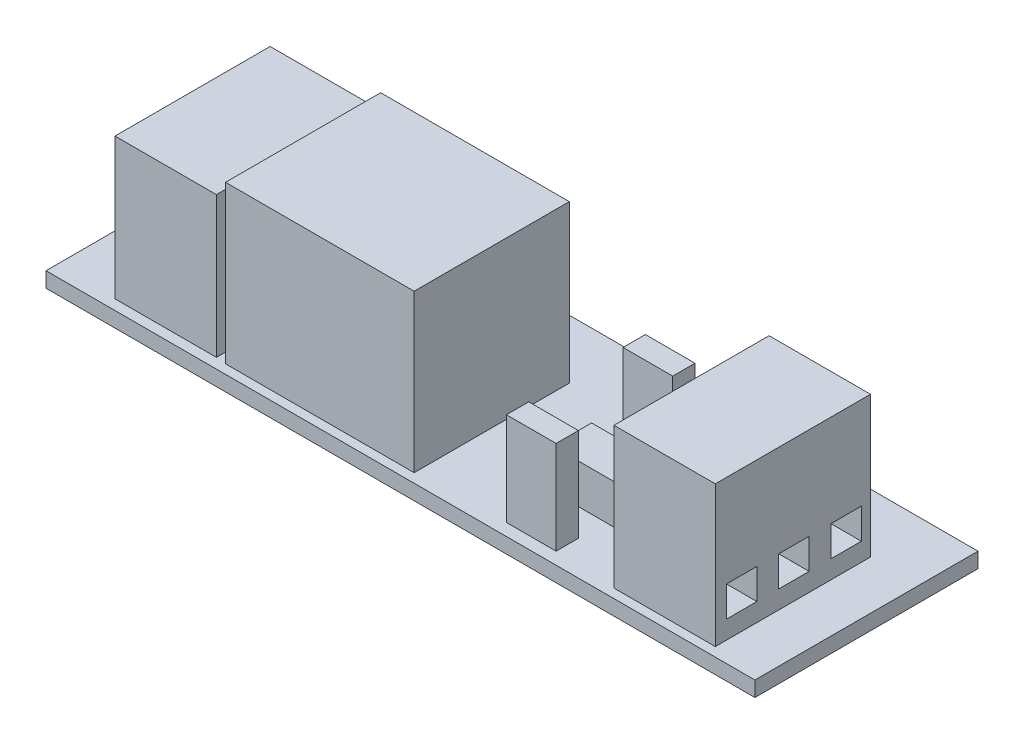
SolidWorks part; units mm, degrees
ref_plane "Front Plane" through (0, 0, 0) normal (0, 0, 1) x (1, 0, 0)
ref_plane "Top Plane" through (0, 0, 0) normal (0, 1, 0) x (1, 0, 0)
ref_plane "Right Plane" through (0, 0, 0) normal (1, 0, 0) x (0, 0, -1)
sketch "Sketch1" plane through (0, 0, 0) normal (0, 1, 0) x (1, 0, 0)
  line L1 (-25.35, 18.6) -> (44.55, 18.6)
  line L2 (-25.35, 18.6) -> (-25.35, -3.4)
  line L3 (-25.35, -3.4) -> (44.55, -3.4)
  line L4 (44.55, 18.6) -> (44.55, -3.4)
  dimension "D1" = 69.9
  dimension "D2" = 22
extrude "Boss-Extrude1" add sketch "Sketch1" along normal blind 1.5
sketch "Sketch2" plane through (0, 1.5, 0) normal (0, 1, 0) x (1, 0, 0)
  line L0 (44.55, -3.4) -> (44.55, 18.6) construction
  line L1 (-8.55, 12.8) -> (10.05, 12.8)
  line L2 (-8.55, 12.8) -> (-8.55, -2.5)
  line L3 (-8.55, -2.5) -> (10.05, -2.5)
  line L4 (10.05, 12.8) -> (10.05, -2.5)
  line L5 (-19.55, 12.9) -> (-9.55, 12.9)
  line L6 (-19.55, 12.9) -> (-19.55, -2.4)
  line L7 (-19.55, -2.4) -> (-9.55, -2.4)
  line L8 (-9.55, 12.9) -> (-9.55, -2.4)
  line L9 (29.75, 12.8) -> (39.75, 12.8)
  line L10 (29.75, 12.8) -> (29.75, -2.5)
  line L11 (29.75, -2.5) -> (39.75, -2.5)
  line L12 (39.75, 12.8) -> (39.75, -2.5)
  line L14 (-25.35, 18.6) -> (-25.35, -3.4) construction
  line L15 (44.55, 18.6) -> (-25.35, 18.6) construction
  dimension "D1" = 15.3
  dimension "D2" = 15.3
  dimension "D3" = 18.6
  dimension "D4" = 10
  dimension "D5" = 14.8
  dimension "D6" = 15.8
  dimension "D7" = 10
  dimension "D8" = 35.4
  dimension "D9" = 21.1
  dimension "D10" = 21
  dimension "D11" = 21.1
  dimension "D12" = 15.3
extrude "Boss-Extrude2" add sketch "Sketch2" along normal blind 15.4 from surface contours L8 L5 L6 L7 | L12 L9 L10 L11 region at (-14.55, 1.5, -5.25) region at (34.75, 1.5, -5.15) starting at face at (9.6, 0, -7.6)
extrude "Boss-Extrude3" add sketch "Sketch2<3>" along normal blind 17 from surface contours L4 L1 L2 L3 region at (0.75, 1.5, -5.15) starting at face at (9.6, 0, -7.6)
sketch "Sketch2<3>" plane through (0, 1.5, 0) normal (0, 1, 0) x (1, 0, 0) same geometry as "Sketch2"
sketch "Sketch3" plane through (-19.55, 0, 0) normal (-1, 0, 0) x (0, 0, 1)
  line L0 (2.4, 15.4) -> (2.4, 1.5) construction
  line L1 (-11.9, 6.3) -> (-8.9, 6.3)
  line L2 (-11.9, 6.3) -> (-11.9, 3.3)
  line L3 (-11.9, 3.3) -> (-8.9, 3.3)
  line L4 (-8.9, 6.3) -> (-8.9, 3.3)
  line L5 (-6.75, 6.3) -> (-3.75, 6.3)
  line L6 (-6.75, 6.3) -> (-6.75, 3.3)
  line L7 (-6.75, 3.3) -> (-3.75, 3.3)
  line L8 (-3.75, 6.3) -> (-3.75, 3.3)
  line L9 (-1.6, 6.3) -> (1.4, 6.3)
  line L10 (-1.6, 6.3) -> (-1.6, 3.3)
  line L11 (-1.6, 3.3) -> (1.4, 3.3)
  line L12 (1.4, 6.3) -> (1.4, 3.3)
  line L13 (-12.9, 15.4) -> (-12.9, 1.5) construction
  line L14 (-18.6, 0) -> (3.4, 0) construction
  dimension "D1" = 3
  dimension "D2" = 3
  dimension "D3" = 3
  dimension "D4" = 1
  dimension "D5" = 1
  dimension "D6" = 2.15
  dimension "D7" = 6.3
  dimension "D8" = 3.3
  dimension "D9" = 3.3
  dimension "D10" = 3.3
  dimension "D11" = 6.3
  dimension "D12" = 6.3
extrude "Cut-Extrude1" cut sketch "Sketch3" against normal blind 8
sketch "Sketch4" plane through (39.75, 0, 0) normal (1, 0, 0) x (0, 0, -1)
  line L1 (11.9, 6.3) -> (8.9, 6.3)
  line L2 (11.9, 6.3) -> (11.9, 3.3)
  line L3 (11.9, 3.3) -> (8.9, 3.3)
  line L4 (8.9, 6.3) -> (8.9, 3.3)
  line L5 (6.75, 6.3) -> (3.75, 6.3)
  line L6 (6.75, 6.3) -> (6.75, 3.3)
  line L7 (6.75, 3.3) -> (3.75, 3.3)
  line L8 (3.75, 6.3) -> (3.75, 3.3)
  line L9 (1.6, 6.3) -> (-1.4, 6.3)
  line L10 (1.6, 6.3) -> (1.6, 3.3)
  line L11 (1.6, 3.3) -> (-1.4, 3.3)
  line L12 (-1.4, 6.3) -> (-1.4, 3.3)
extrude "Cut-Extrude2" cut sketch "Sketch4" against normal blind 8
sketch "Sketch5" plane through (0, 1.5, 0) normal (0, 1, 0) x (1, 0, 0)
  line L0 (29.75, 12.8) -> (29.75, -2.5) construction
  line L1 (18.85, 11.5) -> (23.75, 11.5)
  line L2 (18.85, 11.5) -> (18.85, 9.3)
  line L3 (18.85, 9.3) -> (23.75, 9.3)
  line L4 (23.75, 11.5) -> (23.75, 9.3)
  line L5 (18.85, 0) -> (23.75, 0)
  line L6 (18.85, 0) -> (18.85, -2.2)
  line L7 (18.85, -2.2) -> (23.75, -2.2)
  line L8 (23.75, 0) -> (23.75, -2.2)
  line L9 (18.45, 6.6) -> (24.55, 6.6)
  line L10 (18.45, 6.6) -> (18.45, 2.7)
  line L11 (18.45, 2.7) -> (24.55, 2.7)
  line L12 (24.55, 6.6) -> (24.55, 2.7)
  line L13 (29.75, -2.5) -> (29.75, 12.8) construction
  line L14 (-25.35, -3.4) -> (44.55, -3.4) construction
  line L15 (44.55, 18.6) -> (-25.35, 18.6) construction
  point P20 (21.5, 6.6)
  dimension "D1" = 2.2
  dimension "D2" = 2.2
  dimension "D3" = 4.9
  dimension "D4" = 4.9
  dimension "D5" = 6
  dimension "D6" = 6
  dimension "D7" = 5.2
  dimension "D8" = 6.1
  dimension "D9" = 1.2
  dimension "D10" = 15.9
  dimension "D11" = 3.9
  dimension "D12" = 2.7
extrude "Boss-Extrude5" add sketch "Sketch5" along normal blind 10.7 from surface contours L4 L1 L2 L3 | L8 L5 L6 L7 region at (21.3, 1.5, -10.4) region at (21.3, 1.5, 1.1) starting at face at (9.6, 0, -7.6)
extrude "Boss-Extrude6" add sketch "Sketch5<3>" along normal blind 5.4 from surface contours L12 L9 L10 L11 region at (21.5, 1.5, -4.65) starting at face at (9.6, 0, -7.6)
sketch "Sketch5<3>" plane through (0, 1.5, 0) normal (0, 1, 0) x (1, 0, 0) same geometry as "Sketch5"
sketch "Sketch6" plane through (0, 0, 0) normal (0, -1, 0) x (1, 0, 0)
  line L0 (-25.35, 3.4) -> (44.55, 3.4) construction
  line L1 (-17.05, 2.2) -> (35.95, 2.2)
  line L2 (-17.05, 2.2) -> (-17.05, -12.4)
  line L3 (-17.05, -12.4) -> (35.95, -12.4)
  line L4 (35.95, 2.2) -> (35.95, -12.4)
  line L5 (-25.35, -18.6) -> (-25.35, 3.4) construction
  dimension "D1" = 53
  dimension "D2" = 14.6
  dimension "D3" = 1.2
  dimension "D4" = 8.3
extrude "Boss-Extrude7" add sketch "Sketch6" along normal blind 1 from offset 0
